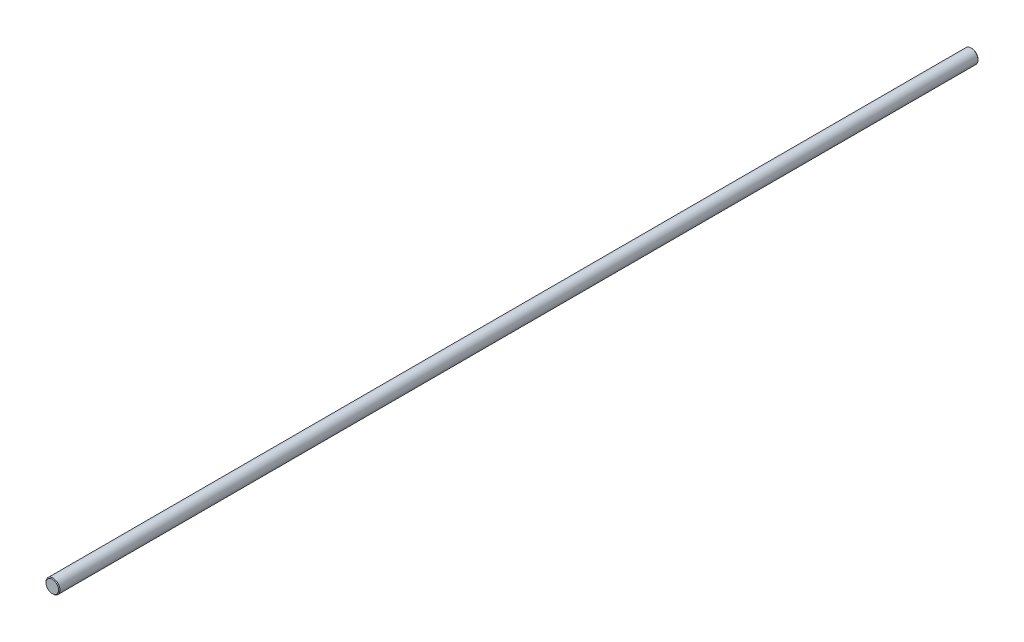
SolidWorks part; units mm, degrees
material "AISI Type A2 Tool Steel"
ref_plane "Front Plane" through (0, 0, 0) normal (0, 0, 1) x (1, 0, 0)
ref_plane "Top Plane" through (0, 0, 0) normal (0, 1, 0) x (1, 0, 0)
ref_plane "Right Plane" through (0, 0, 0) normal (1, 0, 0) x (0, 0, -1)
sketch "Sketch1" plane through (0, 0, 0) normal (0, 0, 1) x (1, 0, 0)
  circle A0 centre (0, 0) radius 4
  dimension "D1" = 8
extrude "Boss-Extrude1" add sketch "Sketch1" along normal blind 528
chamfer "Chamfer1" distance 0.4 angle 45 2 edges at (4, 0, 0) (4, 0, 528)
